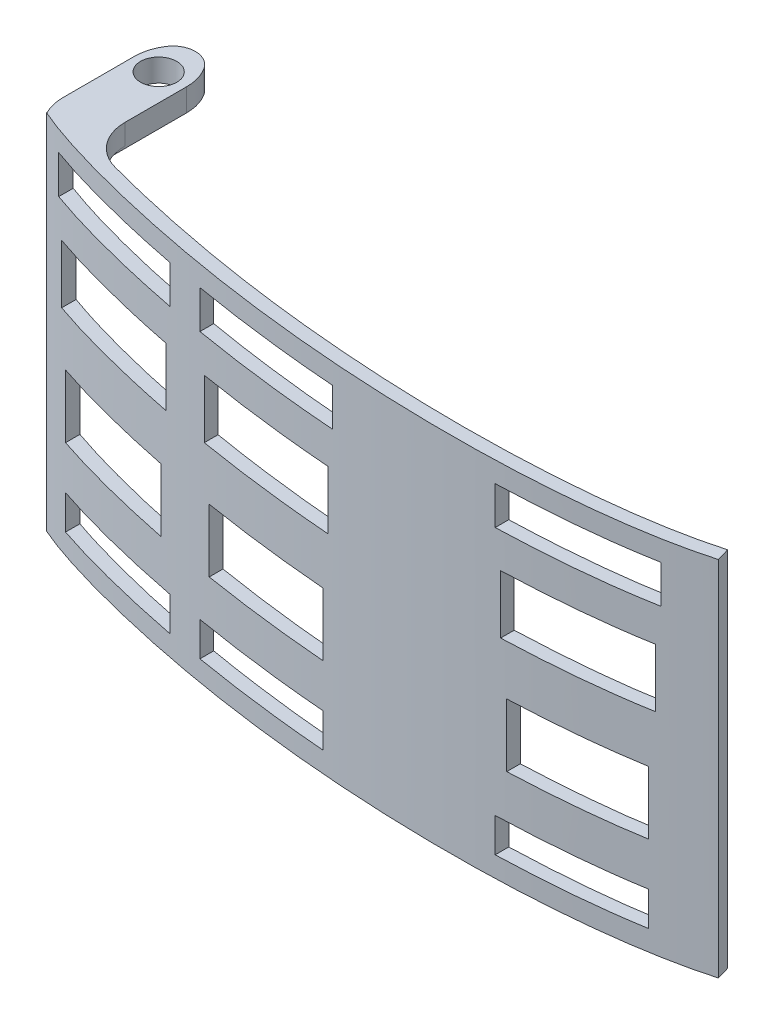
SolidWorks part; units mm, degrees
ref_plane "Front Plane" through (0, 0, 0) normal (0, 0, 1) x (1, 0, 0)
ref_plane "Top Plane" through (0, 0, 0) normal (0, 1, 0) x (1, 0, 0)
ref_plane "Right Plane" through (0, 0, 0) normal (1, 0, 0) x (0, 0, -1)
sketch "Sketch1" plane through (0, 0, 0) normal (0, 1, 0) x (1, 0, 0)
  line L0 (-41.8764, -1.49) -> (-40.6726, 1.2579)
  line L1 (117.7246, -12.7825) -> (116.9055, -9.8965)
  spline S0 degree 3 poles (-41.8764, -1.49) (-32.0931, -5.776) (29.2371, -21.6215) (93.9378, -19.5329) (117.7246, -12.7825) knots 0 0 0 0 0.3026 1 1 1 1
  spline S1 degree 1 poles (-40.6726, 1.2579) (116.9055, -9.8965) knots 0 0 1 1 construction
  spline S2 degree 3 poles (-40.6726, 1.2579) (-40.428, 1.1507) (-39.9451, 0.9434) (-38.9096, 0.515) (-37.5321, -0.0254) (-35.7416, -0.6842) (-33.1875, -1.5704) (-29.7008, -2.6874) (-25.1102, -4.0236) (-20.1731, -5.3396) (-13.2078, -7.0462) (-3.9258, -9.0531) (7.6553, -11.1362) (23.1573, -13.3521) (42.4687, -15.1277) (60.9985, -15.6664) (74.9505, -15.4157) (84.8757, -14.9021) (94.1588, -14.079) (101.2722, -13.149) (106.5347, -12.2684) (110.255, -11.5419) (113.1491, -10.8855) (115.3455, -10.3282) (116.3818, -10.0451) (116.9055, -9.8965) knots 0 0 0 0 0.007812 0.015625 0.03125 0.046875 0.0625 0.09375 0.125 0.15625 0.1875 0.25 0.3125 0.375 0.5 0.625 0.6875 0.75 0.8125 0.875 0.90625 0.9375 0.96875 0.984375 1 1 1 1
  dimension "D1" = 3
  dimension "100" = 160
extrude "Boss-Extrude1" add sketch "Sketch1" along normal blind 80
sketch "Sketch2" plane through (0, 0, 0) normal (0, 0, 1) x (1, 0, 0)
  line L0 (0, 80) -> (0, 0)
  line L3 (117.7246, 80) -> (117.7246, 0) construction
  line L36 (117.7246, 80) -> (-41.8764, 80) construction
  line L42 (164.8319, 40) -> (117.7246, 40) construction
  line L54 (69.2399, 80) -> (69.2399, 0)
  line L56 (-41.8764, 0) -> (117.7246, 0) construction
  line L57 (6.4965, 35.5139) -> (6.4965, 21.612)
  line L58 (-37.3413, 75.4819) -> (-4.0347, 75.4819)
  line L59 (-37.3413, 75.4819) -> (-37.3413, 67.0828)
  line L60 (-37.3413, 67.0828) -> (-4.0347, 67.0828)
  line L61 (-4.0347, 75.4819) -> (-4.0347, 67.0828)
  line L62 (-36.3277, 59.4078) -> (-5.1932, 59.4078)
  line L63 (-36.3277, 59.4078) -> (-36.3277, 46.5196)
  line L64 (-36.3277, 46.5196) -> (-5.1932, 46.5196)
  line L65 (-5.1932, 59.4078) -> (-5.1932, 46.5196)
  line L66 (-35.0244, 35.5139) -> (-6.4965, 35.5139)
  line L67 (-35.0244, 35.5139) -> (-35.0244, 21.612)
  line L68 (-35.0244, 21.612) -> (-6.4965, 21.612)
  line L69 (-6.4965, 35.5139) -> (-6.4965, 21.612)
  line L70 (-35.0244, 12.0545) -> (-4.0347, 12.0545)
  line L71 (-35.0244, 12.0545) -> (-35.0244, 4.5243)
  line L72 (-35.0244, 4.5243) -> (-4.0347, 4.5243)
  line L73 (-4.0347, 12.0545) -> (-4.0347, 4.5243)
  line L74 (35.0244, 21.612) -> (6.4965, 21.612)
  line L75 (35.0244, 35.5139) -> (35.0244, 21.612)
  line L76 (35.0244, 35.5139) -> (6.4965, 35.5139)
  line L77 (5.1932, 59.4078) -> (5.1932, 46.5196)
  line L78 (36.3277, 46.5196) -> (5.1932, 46.5196)
  line L79 (36.3277, 59.4078) -> (36.3277, 46.5196)
  line L80 (36.3277, 59.4078) -> (5.1932, 59.4078)
  line L81 (4.0347, 75.4819) -> (4.0347, 67.0828)
  line L82 (37.3413, 67.0828) -> (4.0347, 67.0828)
  line L83 (37.3413, 75.4819) -> (37.3413, 67.0828)
  line L84 (37.3413, 75.4819) -> (4.0347, 75.4819)
  line L85 (35.0244, 4.5243) -> (4.0347, 4.5243)
  line L86 (4.0347, 12.0545) -> (4.0347, 4.5243)
  line L87 (35.0244, 12.0545) -> (4.0347, 12.0545)
  line L88 (35.0244, 12.0545) -> (35.0244, 4.5243)
  line L89 (74.0834, 12.0545) -> (74.0834, 4.5243)
  line L90 (105.0731, 4.5243) -> (74.0834, 4.5243)
  line L91 (105.0731, 12.0545) -> (105.0731, 4.5243)
  line L92 (105.0731, 12.0545) -> (74.0834, 12.0545)
  line L93 (76.5452, 35.5139) -> (76.5452, 21.612)
  line L94 (105.0731, 21.612) -> (76.5452, 21.612)
  line L95 (105.0731, 35.5139) -> (105.0731, 21.612)
  line L96 (105.0731, 35.5139) -> (76.5452, 35.5139)
  line L97 (75.2419, 59.4078) -> (75.2419, 46.5196)
  line L98 (106.3764, 46.5196) -> (75.2419, 46.5196)
  line L99 (106.3764, 59.4078) -> (106.3764, 46.5196)
  line L100 (106.3764, 59.4078) -> (75.2419, 59.4078)
  line L101 (74.0834, 75.4819) -> (74.0834, 67.0828)
  line L102 (107.3901, 67.0828) -> (74.0834, 67.0828)
  line L103 (107.3901, 75.4819) -> (107.3901, 67.0828)
  line L104 (107.3901, 75.4819) -> (74.0834, 75.4819)
extrude "Cut-Extrude1" cut sketch "Sketch2" against normal through all both and the other way through all contours L61 L58 L59 L60 | L65 L62 L63 L64 | L69 L66 L67 L68 | L73 L70 L71 L72 | L88 L87 L86 L85 | L75 L76 L57 L74 | L79 L80 L77 L78 | L83 L84 L81 L82 | L95 L96 L93 L94 | L92 L89 L90 L91 | L98 L97 L100 L99 | L104 L101 L102 L103 region at (20.7604, 28.563, 0) region at (-20.688, 71.2824, 0) region at (-20.7604, 52.9637, 0) region at (-20.7604, 28.563, 0) region at (-19.5295, 8.2894, 0) region at (20.7604, 52.9637, 0) region at (20.688, 71.2824, 0) region at (19.5295, 8.2894, 0) region at (90.8092, 28.563, 0)
sketch "Sketch3" plane through (0, 80, 0) normal (0, 1, 0) x (1, 0, 0)
  line L0 (-42.8907, -1.2036) -> (-31.3134, -2.5995)
  line L5 (-42.8907, 28.9307) -> (-31.3134, 28.9307)
  line L6 (-42.8907, 28.9307) -> (-42.8907, -1.2036)
  line L8 (-31.3134, 28.9307) -> (-31.3134, -2.5995)
  circle A0 centre (-37.2547, 18.6805) radius 4
  point P1 (-36.9276, 13.4463)
  point P2 (-37.2547, 18.6805)
  dimension "D1" = 8
extrude "Boss-Extrude2" add sketch "Sketch3" against normal blind 5
fillet "Fillet1" radius 10 1 edges at (-31.3134, 77.741, 2.1644)
fillet "Fillet2" radius 10 3 edges at (-42.8907, 77.5, 1.2036) (-42.8907, 77.5, -28.9307) (-31.3134, 77.5, -28.9307)
fillet "Fillet3" radius 5 1 edges at (-37.102, 77.5, -28.0007)
